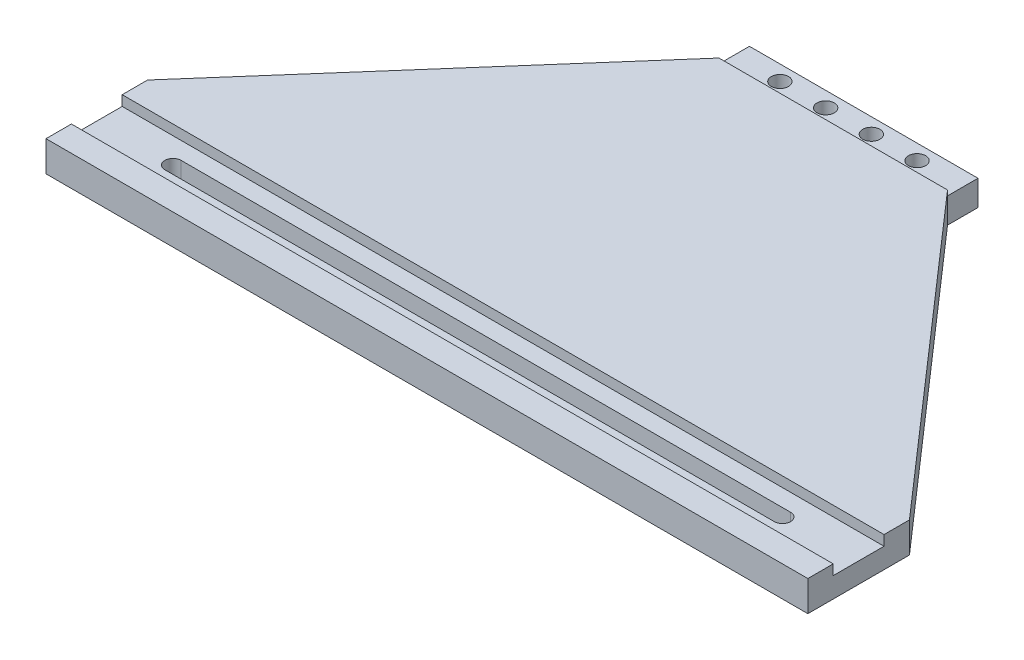
SolidWorks part; units mm, degrees
material "Сплав 2024"
ref_plane "Спереди" through (0, 0, 0) normal (0, 0, 1) x (1, 0, 0)
ref_plane "Сверху" through (0, 0, 0) normal (0, 1, 0) x (1, 0, 0)
ref_plane "Справа" through (0, 0, 0) normal (1, 0, 0) x (0, 0, -1)
sketch "Эскиз1" plane through (0, 0, 0) normal (0, 1, 0) x (1, 0, 0)
  line L0 (-22.5, 0) -> (22.5, 0) construction
  line L1 (-22.5, 3) -> (22.5, 3)
  line L2 (-22.5, 3) -> (-22.5, -3)
  line L3 (-22.5, -3) -> (22.5, -3) construction
  line L4 (22.5, 3) -> (22.5, -3)
  line L5 (-22.5, 3) -> (22.5, -3) construction
  line L6 (-22.5, -3) -> (22.5, 3) construction
  line L7 (0, 3) -> (0, -3) construction
  line L8 (-22.5, -3) -> (-75, -63)
  line L9 (-75, -63) -> (-75, -83)
  line L10 (-75, -83) -> (75, -83)
  line L11 (75, -83) -> (75, -63)
  line L12 (75, -63) -> (22.5, -3)
  line L13 (0, -3) -> (0, -163) construction
  line L14 (75, -63) -> (-75, -63) construction
  line L15 (-13.5, 3) -> (-13.5, -3) construction
  line L16 (-4.5, 3) -> (-4.5, -3) construction
  line L17 (4.5, 3) -> (4.5, -3) construction
  line L18 (13.5, 3) -> (13.5, -3) construction
  point P0 (0, 0)
  point P10 (0, -83)
  dimension "D1" = 45
  dimension "D2" = 6
  dimension "D3" = 150
  dimension "D4" = 80
  dimension "D5" = 20
  dimension "D6" = 9
  dimension "D7" = 9
  dimension "D8" = 9
  dimension "D9" = 9
extrude "Бобышка-Вытянуть1" add sketch "Эскиз1" along normal blind 6
sketch "Эскиз2" plane through (0, 6, 0) normal (0, 1, 0) x (1, 0, 0)
  line L0 (75, -83) -> (75, -63) construction
  line L1 (-75, -78) -> (75, -78)
  line L2 (-75, -78) -> (-75, -68)
  line L3 (-75, -68) -> (75, -68)
  line L4 (75, -78) -> (75, -68)
  line L5 (-75, -83) -> (75, -83) construction
  dimension "D1" = 10
  dimension "D2" = 5
extrude "Вырез-Вытянуть1" cut sketch "Эскиз2" against normal blind 2
sketch "Эскиз3" plane through (0, 6, 0) normal (0, 1, 0) x (1, 0, 0)
  line L1 (-22.5, 3) -> (22.5, 3)
  line L2 (-22.5, 3) -> (-22.5, -3)
  line L3 (-22.5, -3) -> (22.5, -3)
  line L4 (22.5, 3) -> (22.5, -3)
extrude "Вырез-Вытянуть2" cut sketch "Эскиз3" against normal blind 1
hole_wizard "Отверстие с зазором M31" positions "Эскиз8" profile "Эскиз7" hole size "M3" standard "Ansi Metric" end condition through all
sketch "Эскиз8" plane through (0, 0, 0) normal (0, -1, 0) x (-1, 0, 0)
  line L0 (-13.5, 3) -> (-13.5, -3) construction
  line L1 (-4.5, 3) -> (-4.5, -3) construction
  line L2 (4.5, 3) -> (4.5, -3) construction
  line L3 (13.5, 3) -> (13.5, -3) construction
  point P0 (-13.5, 0)
  point P4 (-4.5, 0)
  point P8 (4.5, 0)
  point P12 (13.5, 0)
sketch "Эскиз7" plane through (13.5, 0, 0) normal (1, 0, 0) x (0, 0, -1)
  line L0 (0, 0) -> (0, 6)
  line L1 (0, 6) -> (1.7, 6)
  line L2 (1.7, 6) -> (1.7, 0)
  line L5 (1.7, 0) -> (0, 0)
  line L11 (0, -6.35) -> (0, 107.95) construction
  dimension "Диаметр сквозного отверстия" = 3.4
  dimension "Глубина сквозного отверстия" = 6
sketch "Эскиз9" plane through (0, 4, 0) normal (0, 1, 0) x (1, 0, 0)
  line L0 (-60, -73) -> (60, -73) construction
  line L1 (-60, -71.4) -> (60, -71.4)
  line L2 (-60, -74.6) -> (60, -74.6)
  line L3 (0, -68) -> (0, -78) construction
  line L4 (75, -68) -> (-75, -68) construction
  line L5 (-75, -78) -> (75, -78) construction
  arc A0 (-60, -71.4) -> (-60, -74.6) centre (-60, -73) ccw
  arc A1 (60, -74.6) -> (60, -71.4) centre (60, -73) ccw
  point P2 (0, -73)
  dimension "D1" = 1.6
  dimension "D2" = 120
extrude "Вырез-Вытянуть3" cut sketch "Эскиз9" against normal through all
equation "\"D6@Эскиз1\"=\"D1@Эскиз1\"/5"
equation "\"D7@Эскиз1\"=\"D6@Эскиз1\""
equation "\"D8@Эскиз1\"=\"D6@Эскиз1\""
equation "\"D9@Эскиз1\"=\"D6@Эскиз1\""
